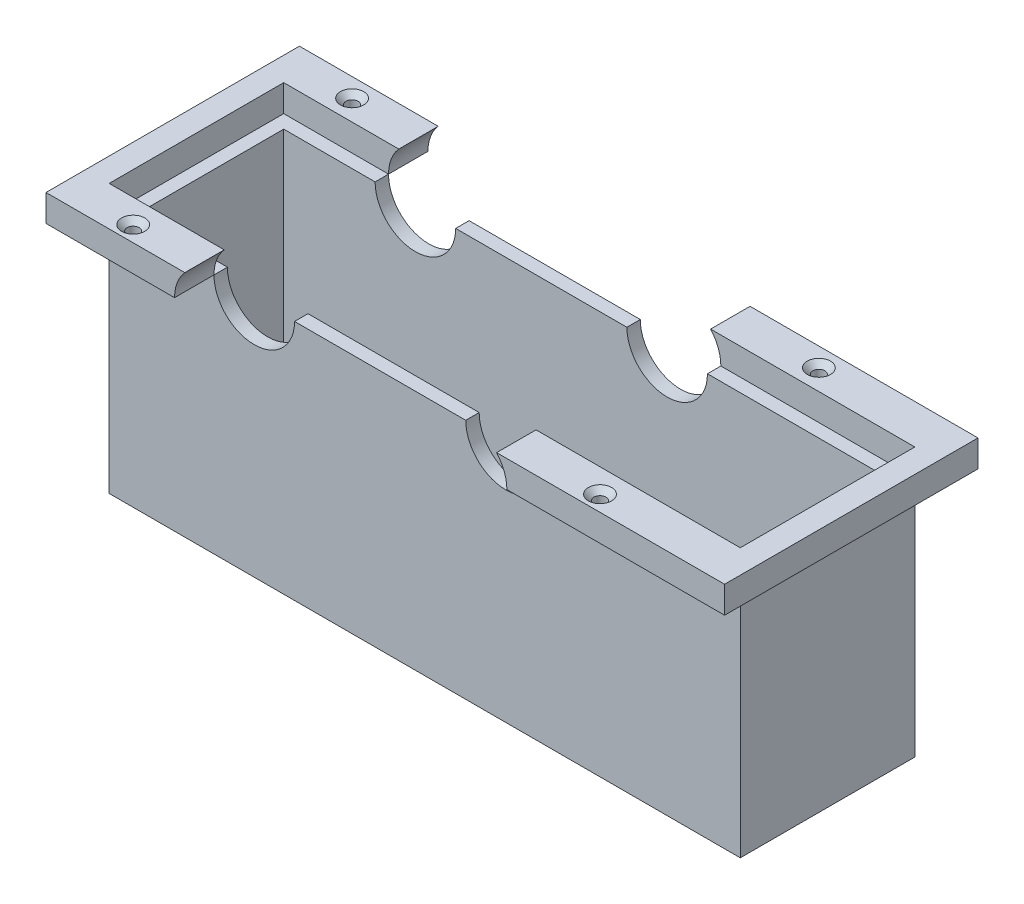
SolidWorks part; units mm, degrees
note: The reader was unsure of these and kept them because the rebuilt part matched: shared geometry of "Sketch2<4>".
ref_plane "Front Plane" through (0, 0, 0) normal (0, 0, 1) x (1, 0, 0)
ref_plane "Top Plane" through (0, 0, 0) normal (0, 1, 0) x (1, 0, 0)
ref_plane "Right Plane" through (0, 0, 0) normal (1, 0, 0) x (0, 0, -1)
sketch "Sketch1" plane through (0, 0, 0) normal (0, 1, 0) x (1, 0, 0)
  line L1 (-225, -55) -> (225, -55)
  line L2 (-225, -55) -> (-225, 55)
  line L3 (-225, 55) -> (225, 55)
  line L4 (225, -55) -> (225, 55)
  line L5 (-225, -55) -> (225, 55) construction
  line L6 (-225, 55) -> (225, -55) construction
  point P0 (0, 0)
  dimension "D1" = 110
  dimension "D2" = 450
extrude "Boss-Extrude1" add sketch "Sketch1" along normal blind 170
shell "Shell1" thickness 10
sketch "Sketch2" plane through (0, 0, 65) normal (0, 0, 1) x (1, 0, 0)
  line L0 (-235, 170) -> (235, 170) construction
  circle A0 centre (-126.9504, 170) radius 30
  circle A1 centre (60.5496, 170) radius 30
  dimension "D1" = 60
  dimension "D2" = 60
  dimension "D3" = 187.5
extrude "Cut-Extrude1" cut sketch "Sketch2" against normal blind 250
sketch "Sketch4" plane through (0, 170, 0) normal (0, -1, 0) x (-1, 0, 0)
  line L1 (252.6801, 94.3694) -> (-252.6801, 94.3694)
  line L2 (252.6801, 94.3694) -> (252.6801, -94.3694)
  line L3 (252.6801, -94.3694) -> (-252.6801, -94.3694)
  line L4 (-252.6801, 94.3694) -> (-252.6801, -94.3694)
  line L5 (252.6801, 94.3694) -> (-252.6801, -94.3694) construction
  line L6 (252.6801, -94.3694) -> (-252.6801, 94.3694) construction
  line L7 (235, 65) -> (-235, 65)
  line L8 (235, 65) -> (235, -65)
  line L9 (235, -65) -> (-235, -65)
  line L10 (-235, 65) -> (-235, -65)
  line L11 (235, 65) -> (-235, -65) construction
  line L12 (235, -65) -> (-235, 65) construction
  point P0 (0, 0)
  point P6 (0, 0)
extrude "Boss-Extrude3" add sketch "Sketch4" against normal blind 20 separate body
extrude "Cut-Extrude4" cut sketch "Sketch2<4>" along normal blind 75 and the other way blind 265
sketch "Sketch2<4>" plane through (0, 0, 65) normal (0, 0, 1) x (1, 0, 0) same geometry as "Sketch2"
hole_wizard "CSK for M8 Countersunk Flat Head Screw1" positions "Sketch8" profile "Sketch7" countersink size "M8" standard "ISO"
sketch "Sketch8" plane through (0, 190, 0) normal (0, 1, 0) x (1, 0, 0)
  point P0 (-199.4434, 80.3452)
  point P2 (-199.4434, -82.6724)
  point P4 (-34.4895, -82.6724)
  point P6 (-34.4895, 80.3452)
  point P8 (148.1982, 80.3452)
  point P10 (148.1982, -82.6724)
sketch "Sketch7" plane through (-199.4434, 190, -80.3452) normal (1, 0, 0) x (0, 0, 1)
  line L0 (0, 0) -> (0, 200)
  line L1 (0, 200) -> (4.5, 200)
  line L2 (4.5, 200) -> (4.5, 4.15)
  line L3 (4.5, 4.15) -> (8.65, 0)
  line L5 (8.65, 0) -> (0, 0)
  line L6 (-4.5, 4.15) -> (-8.65, 0) construction
  line L11 (0, -6.35) -> (0, 107.95) construction
  dimension "Thru Hole Dia." = 9
  dimension "Thru Hole Depth" = 200
  dimension "Near C'Sink Dia." = 17.3
  dimension "Near C'Sink Angle" = 90
